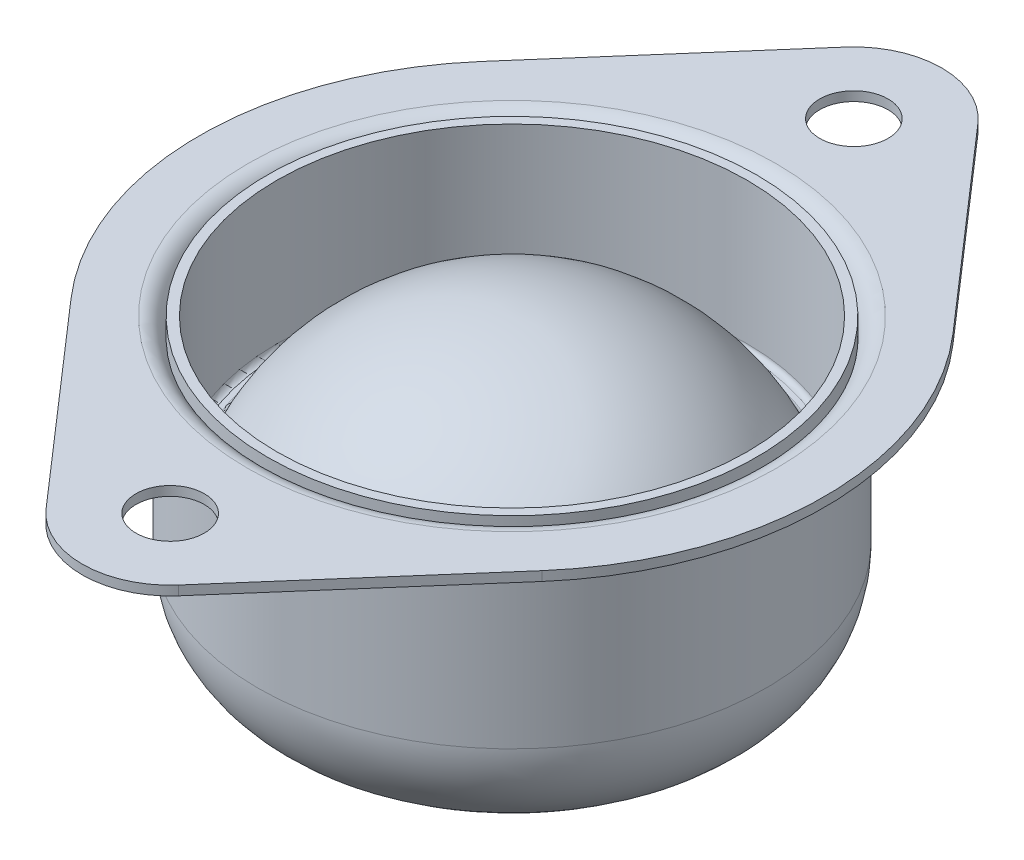
SolidWorks part; units mm, degrees
ref_plane "Front" through (0, 0, 0) normal (0, 0, 1) x (1, 0, 0)
ref_plane "Top" through (0, 0, 0) normal (0, 1, 0) x (1, 0, 0)
ref_plane "Right" through (0, 0, 0) normal (1, 0, 0) x (0, 0, -1)
sketch "Sketch1" plane through (0, 0, 0) normal (0, 1, 0) x (1, 0, 0)
  line L0 (0, -27.7812) -> (0, 27.7812) construction
  line L1 (19.1457, -16.6914) -> (5.3847, -32.4757)
  line L2 (-5.3847, -32.4757) -> (-19.1457, -16.6914)
  line L3 (-5.3847, 32.4757) -> (-19.1457, 16.6914)
  line L4 (19.1457, 16.6914) -> (5.3847, 32.4757)
  circle A0 centre (0, 0) radius 20.6375 construction
  arc A1 (19.1457, -16.6914) -> (19.1457, 16.6914) centre (0, 0) ccw
  arc A2 (5.3847, 32.4757) -> (-5.3847, 32.4757) centre (0, 27.7812) ccw
  arc A3 (-5.3847, -32.4757) -> (5.3847, -32.4757) centre (0, -27.7812) ccw
  arc A4 (-19.1457, 16.6914) -> (-19.1457, -16.6914) centre (0, 0) ccw
  circle A5 centre (0, 27.7812) radius 2.7781
  circle A6 centre (0, -27.7812) radius 2.7781
  point P5 (0, 0)
  dimension "D1" = 41.275
  dimension "D3" = 50.8
  dimension "D4" = 69.85
  dimension "D5" = 5.5562
  dimension "D2" = 55.5625
extrude "Boss-Extrude1" add sketch "Sketch1" along normal blind 0.762
ref_axis "Axis1" through (0, -0.0381, 0) along (0, 1, 0)
sketch "Sketch2" plane through (0, 0, 0) normal (0, -1, 0) x (1, 0, 0)
  circle A0 centre (0, 0) radius 20.6375 construction
  circle A1 centre (0, 0) radius 20.6375
extrude "Boss-Extrude2" add sketch "Sketch2" along normal offset from surface (23.8442 mm away) 24.6062 up to face at (0, 0.762, -25.0031)
fillet "Fillet1" radius 8.7312 1 edges at (0, -23.8442, 20.6375)
shell "Shell1" thickness 0.762 removed face at (0, 0.762, -25.0031)
fillet "Fillet2" radius 1.5875 2 edges at (0, 0, 20.6375) (0, 0.762, 19.8755)
sketch "Sketch6" plane through (0, -23.8443, 0) normal (0, -1, 0) x (1, 0, 0)
  circle A1 centre (0, 0) radius 11.9062
  circle A2 centre (0, 0) radius 11.9062
  dimension "D1" = 0
extrude "Cut-Extrude3" cut sketch "Sketch6" against normal up to surface (0.762 mm away) up to face at (0, -23.0822, 11.9062)
sketch "Sketch7" plane through (0, 0.762, 0) normal (0, 1, 0) x (1, 0, 0)
  circle A0 centre (0, 0) radius 19.8755 construction
  circle A1 centre (0, 0) radius 19.8755
extrude "Boss-Extrude3" add sketch "Sketch7" against normal blind 12.7 separate body
sketch "Sketch8" plane through (0, 0, 0) normal (1, 0, 0) x (0, 0, -1)
  line L0 (-19.8755, -11.938) -> (19.8755, -11.938) construction
  line L1 (0, 0) -> (0, -11.938)
  line L2 (0, -11.938) -> (-17.4625, -11.938)
  arc A0 (-17.4625, -11.938) -> (0, 0) centre (0, -18.7408) cw
  arc A1 (0, 0) -> (17.4625, -11.938) centre (0, -18.7408) cw construction
  dimension "D1" = 34.925
revolve "Cut-Revolve1" cut sketch "Sketch8" angle 360 about axis through (0, -0.0381, 0) along (0, 1, 0)
fillet "Fillet3" radius 1.1906 2 edges at (0, -11.938, 19.8755) (0, -11.938, -17.4625)
shell "Shell2" thickness 0.762 removed face at (0, 0.762, 19.8755)
sketch "Sketch3" plane through (0, 0, 0) normal (1, 0, 0) x (0, 0, -1)
  line L0 (16.6914, 0.762) -> (-16.6914, 0.762) construction
  line L1 (0, -29.4005) -> (0, -4.0005)
  arc A0 (0, -4.0005) -> (0, -29.4005) centre (0, -16.7005) ccw
  point P8 (0, -16.7005)
  dimension "D1" = 25.4
  dimension "D2" = 30.1625
revolve "Revolve1" add sketch "Sketch3" angle 360 about axis through (0, -106.8222, 0) along (0, 1, 0)
